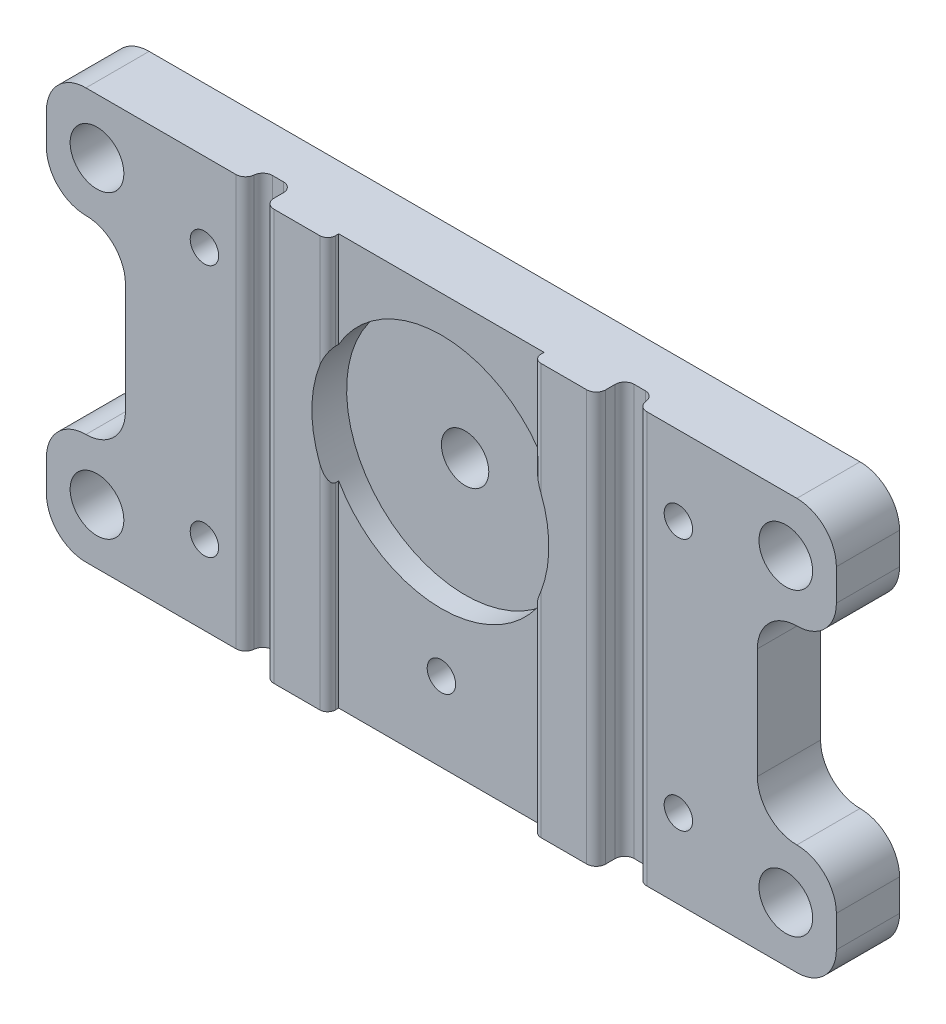
SolidWorks part; units mm, degrees
material "Nylon 101"
ref_plane "Ebene vorne" through (0, 0, 0) normal (0, 0, 1) x (1, 0, 0)
ref_plane "Ebene oben" through (0, 0, 0) normal (0, 1, 0) x (1, 0, 0)
ref_plane "Ebene rechts" through (0, 0, 0) normal (1, 0, 0) x (0, 0, -1)
sketch "body-s" plane through (0, 0, 0) normal (0, 0, 1) x (1, 0, 0)
  line L0 (0, 13) -> (0, -13) construction
  line L1 (-20, 13) -> (20, 13)
  line L2 (-20, 13) -> (-20, -13)
  line L3 (-20, -13) -> (20, -13)
  line L4 (20, 13) -> (20, -13)
  line L5 (-20, 13) -> (20, -13) construction
  line L6 (-20, -13) -> (20, 13) construction
  line L7 (-17, 13) -> (-17, -13) construction
  line L8 (17, 13) -> (17, -13) construction
  line L9 (15, 13) -> (15, -13) construction
  line L10 (-15, 13) -> (-15, -13) construction
  line L11 (-20, 8) -> (20, 8) construction
  line L12 (-20, -8) -> (20, -8) construction
  circle A0 centre (-15, 8) radius 0.9
  circle A1 centre (15, 8) radius 0.9
  circle A2 centre (15, -8) radius 0.9
  circle A3 centre (-15, -8) radius 0.9
  circle A4 centre (0, -8) radius 0.9
  point P0 (0, 0)
  dimension "D7" = 1.8
  dimension "D8" = 5
  dimension "D1" = 26
  dimension "D2" = 40
  dimension "D3" = 3
  dimension "D4" = 3
  dimension "D5" = 2
  dimension "D6" = 2
  dimension "D9" = 5
extrude "body" add sketch "body-s" along normal mid plane 4
sketch "cutting-s" plane through (0, 0, -2) normal (0, 0, -1) x (-1, 0, 0)
  line L0 (-15, 8.9) -> (-15, -8.9) construction
  line L1 (-15.9, 8) -> (15.9, 8) construction
  line L2 (15, 8.9) -> (15, -8.9) construction
  line L3 (-15.9, -8) -> (15.9, -8) construction
  circle A0 centre (-15, 8) radius 0.9 construction
  circle A1 centre (-15, -8) radius 0.9 construction
  circle A2 centre (15, 8) radius 0.9 construction
  circle A3 centre (15, -8) radius 0.9 construction
  circle A4 centre (-15, 8) radius 3.5
  circle A5 centre (15, 8) radius 3.5
  circle A6 centre (15, -8) radius 3.5
  circle A7 centre (-15, -8) radius 3.5
  circle A8 centre (0, -8) radius 3.5
  dimension "D1" = 7
extrude "cutting" cut sketch "cutting-s" against normal blind 3
sketch "wing-s" plane through (0, 0, 2) normal (0, 0, 1) x (1, 0, 0)
  line L0 (-25, 9.5) -> (-20, 9.5) construction
  line L1 (-20, 13) -> (-25, 13)
  line L2 (-20, 13) -> (-20, 6)
  line L3 (-20, 6) -> (-25, 6)
  line L4 (-25, 13) -> (-25, 6)
  line L5 (25, 9.5) -> (20, 9.5) construction
  line L6 (20, 13) -> (25, 13)
  line L7 (20, 13) -> (20, 6)
  line L8 (20, 6) -> (25, 6)
  line L9 (25, 13) -> (25, 6)
  circle A0 centre (-21.8, 9.5) radius 1.7
  circle A1 centre (21.8, 9.5) radius 1.7
  dimension "D1" = 3.2
  dimension "D4" = 3.4
  dimension "D7" = 3.4
  dimension "D2" = 5
  dimension "D3" = 7
  dimension "D5" = 5
  dimension "D6" = 7
  dimension "D8" = 3.2
extrude "wing" add sketch "wing-s" against normal blind 4
pattern_linear "Lineares Muster2" count 2 spacing 19 along (0, -1, 0) of "wing"
fillet "Verrundung2" radius 2.5 12 edges at (25, -13, 0) (-25, -13, 0) (-25, -6, 0) (-20, -6, 0) (-25, 6, 0) (-25, 13, 0) (25, 13, 0) (25, -6, 0) (20, -6, 0) (25, 6, 0)
sketch "glides-s" plane through (0, 0, 2) normal (0, 0, 1) x (1, 0, 0)
  line L0 (0, 13) -> (0, -13) construction
  line L1 (22.5, 13) -> (-22.5, 13) construction
  line L2 (-22.5, -13) -> (22.5, -13) construction
  line L4 (-12.7, 13) -> (-3.5, 13)
  line L5 (-12.7, 13) -> (-12.7, -13)
  line L6 (-12.7, -13) -> (-3.5, -13)
  line L7 (-3.5, 13) -> (-3.5, -13)
  line L8 (3.5, 13) -> (12.7, 13)
  line L9 (3.5, 13) -> (3.5, -13)
  line L10 (3.5, -13) -> (12.7, -13)
  line L11 (12.7, 13) -> (12.7, -13)
  dimension "D1" = 9.2
  dimension "D2" = 3.5
  dimension "D3" = 9.2
  dimension "D4" = 3.5
extrude "glides" add sketch "glides-s" along normal blind 0.7
sketch "gear-h" plane through (0, 0, 2) normal (0, 0, 1) x (1, 0, 0)
  line L0 (0, 13) -> (0, -13) construction
  line L1 (3.5, 13) -> (-3.5, 13) construction
  line L2 (-3.5, -13) -> (3.5, -13) construction
  circle A0 centre (0, 3.2) radius 7.5
  dimension "D1" = 15
  dimension "D2" = 9.8
extrude "gearhole" cut sketch "gear-h" along normal mid plane 3
sketch "bore-s" plane through (0, 0, 2) normal (0, 0, 1) x (1, 0, 0)
  line L0 (0, 13) -> (0, -13) construction
  line L1 (3.5, 13) -> (-3.5, 13) construction
  line L2 (-3.5, -13) -> (3.5, -13) construction
  circle A0 centre (0, 3.2) radius 1.5
  dimension "D1" = 9.8
  dimension "D2" = 3
extrude "Shaft-bore" cut sketch "bore-s" against normal through all both and the other way through all
chamfer "Fase2" distance 3 angle 45 1 edges at (11.5, 8, 1)
chamfer "Fase3" distance 3 angle 45 4 edges at (-18.5, -8, 1) (-18.5, 8, 1) (-3.5, -8, 1) (11.5, -8, 1)
sketch "railcut" plane through (0, 0, 2.7) normal (0, 0, 1) x (1, 0, 0)
  line L0 (-12.4, 13) -> (-12.4, -13) construction
  line L1 (-3.5, 13) -> (-12.7, 13) construction
  line L2 (-12.7, -13) -> (-3.5, -13) construction
  line L3 (12.4, 13) -> (12.4, -13) construction
  line L4 (12.7, 13) -> (3.5, 13) construction
  line L5 (3.5, -13) -> (12.7, -13) construction
  line L6 (-12.7, 13) -> (-12.7, -13) construction
  line L7 (12.7, -13) -> (12.7, 13) construction
  line L9 (-12.4, 13) -> (-10.5, 13)
  line L10 (-12.4, 13) -> (-12.4, -13)
  line L11 (-12.4, -13) -> (-10.5, -13)
  line L12 (-10.5, 13) -> (-10.5, -13)
  line L13 (12.4, 13) -> (10.5, 13)
  line L14 (12.4, 13) -> (12.4, -13)
  line L15 (12.4, -13) -> (10.5, -13)
  line L16 (10.5, 13) -> (10.5, -13)
  dimension "D1" = 0.3
  dimension "D2" = 0.3
  dimension "D3" = 1.9
  dimension "D4" = 1.9
extrude "rail-cut" cut sketch "railcut" against normal blind 1.8
sketch "edge" plane through (0, 0, 2.7) normal (0, 0, 1) x (1, 0, 0)
  line L1 (-12.7, 13) -> (-12.4, 13)
  line L2 (-12.7, 13) -> (-12.7, -13)
  line L3 (-12.7, -13) -> (-12.4, -13)
  line L4 (-12.4, 13) -> (-12.4, -13)
  line L5 (12.4, 13) -> (12.7, 13)
  line L6 (12.4, 13) -> (12.4, -13)
  line L7 (12.4, -13) -> (12.7, -13)
  line L8 (12.7, 13) -> (12.7, -13)
extrude "cut-edge" cut sketch "edge" against normal blind 0.7
fillet "Verrundung6" radius 0.6 2 edges at (12.4, 0, 2) (-12.4, 0, 2)
fillet "Verrundung7" radius 0.6 4 edges at (12.4, 0, 0.9) (10.5, 0, 0.9) (-12.4, 0, 0.9) (-10.5, 0, 0.9)
fillet "Verrundung8" radius 0.6 2 edges at (-10.5, 0, 2.7) (10.5, 0, 2.7)
sketch "glide-space" plane through (0, 0, 2.7) normal (0, 0, 1) x (1, 0, 0)
  line L0 (-3.5, 13) -> (-9.9, 13) construction
  line L1 (-6.5, 13) -> (-3.5, 13)
  line L2 (-6.5, 13) -> (-6.5, -13)
  line L3 (-6.5, -13) -> (-3.5, -13)
  line L4 (-3.5, 13) -> (-3.5, -13)
  line L6 (3.5, -13) -> (9.9, -13) construction
  line L7 (3.5, 13) -> (6.5, 13)
  line L8 (3.5, 13) -> (3.5, -13)
  line L9 (3.5, -13) -> (6.5, -13)
  line L10 (6.5, 13) -> (6.5, -13)
  dimension "D1" = 3
  dimension "D2" = 3
extrude "glide-space-rack-spur" cut sketch "glide-space" against normal blind 0.7
fillet "Verrundung10" radius 0.5 1 edges at (-6.5, 9.9708, 2.7)
fillet "Verrundung11" radius 0.5 1 edges at (-6.5, -6.7708, 2.7)
fillet "Verrundung12" radius 0.5 2 edges at (6.5, 9.9708, 2.7) (6.5, -6.7708, 2.7)
